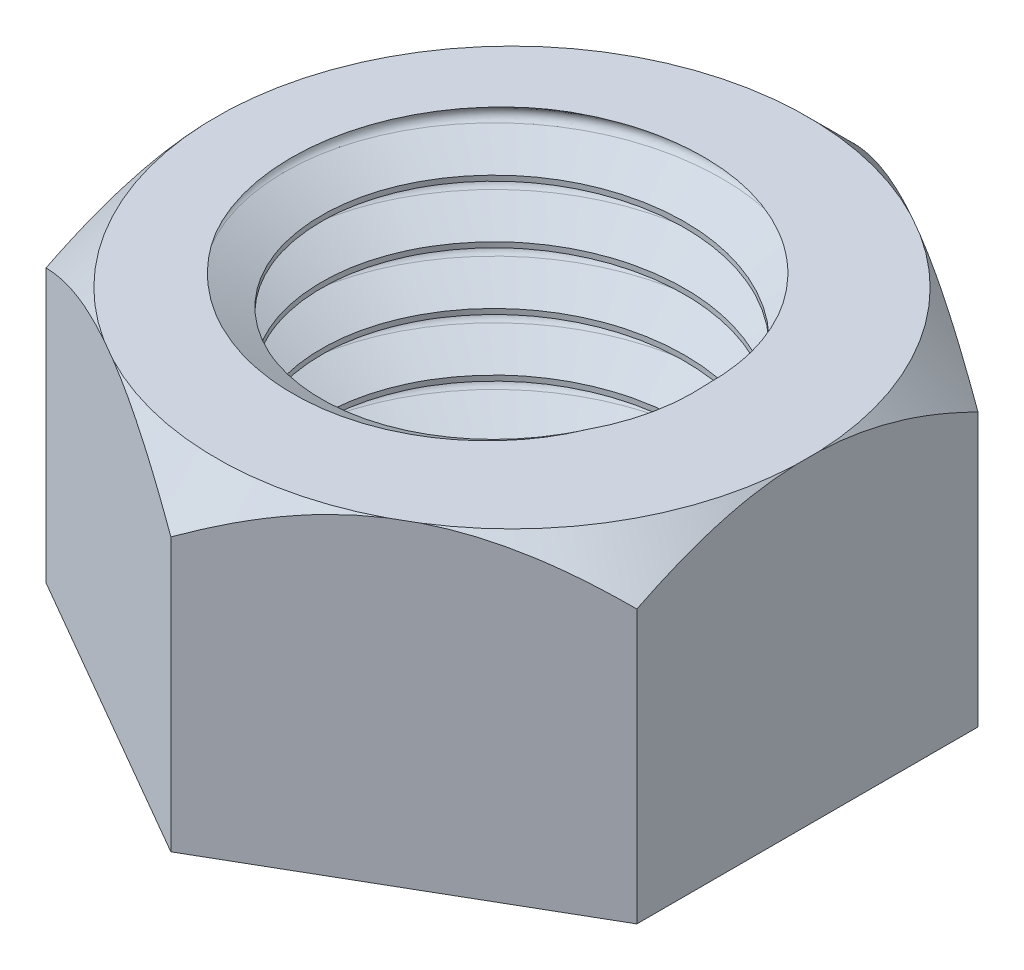
SolidWorks part; units mm, degrees
ref_plane "Alzado" through (0, 0, 0) normal (0, 0, 1) x (1, 0, 0)
ref_plane "Planta" through (0, 0, 0) normal (0, 1, 0) x (1, 0, 0)
ref_plane "Vista lateral" through (0, 0, 0) normal (1, 0, 0) x (0, 0, -1)
sketch "Sketch1" plane through (0, 0, 0) normal (0, 1, 0) x (1, 0, 0)
  line L1 (6.5, -3.7528) -> (6.5, 3.7528)
  line L2 (6.5, 3.7528) -> (0, 7.5056)
  line L3 (0, 7.5056) -> (-6.5, 3.7528)
  line L4 (-6.5, 3.7528) -> (-6.5, -3.7528)
  line L5 (-6.5, -3.7528) -> (0, -7.5056)
  line L6 (0, -7.5056) -> (6.5, -3.7528)
  circle A0 centre (0, 0) radius 6.5 construction
  circle A1 centre (0, 0) radius 4
  dimension "D2" = 8
  dimension "D1" = 13
extrude "Boss-Extrude1" add sketch "Sketch1" along normal blind 7
sketch "Sketch2" plane through (0, 7, 0) normal (0, 1, 0) x (1, 0, 0)
  circle A0 centre (0, 0) radius 4 construction
  circle A1 centre (0, 0) radius 4
curve "Helix/Spiral1" pitch 1.27 height 7.62 turns 6
sketch "Sketch3" plane through (0, 0, 0) normal (0, 0, 1) x (1, 0, 0)
  line L0 (-3.9127, 0.0452) -> (-4.813, -0.4235)
  line L1 (-4.813, -0.7322) -> (-3.9127, -1.2009)
  line L2 (-3.9127, -1.2009) -> (-3.9127, 0.0452)
  line L3 (-4.7327, -0.5778) -> (-3.9127, -0.5778) construction
  arc A0 (-4.813, -0.4235) -> (-4.813, -0.7322) centre (-4.7327, -0.5778) ccw
  spline S0 degree 3 poles (-4, 7) (-4, 6.9737) (-3.7917, 6.9205) (-2.9021, 6.8413) (-1.5706, 6.7619) (0, 6.6825) (1.5706, 6.6031) (2.9021, 6.5238) (3.7917, 6.4444) (4.1041, 6.365) (3.7917, 6.2856) (2.9021, 6.2063) (1.1268, 6.1004) (-1.1268, 5.9946) (-2.9021, 5.8888) (-3.7917, 5.8094) (-4.1041, 5.73) (-3.7917, 5.6506) (-2.9021, 5.5713) (-1.1268, 5.4654) (1.1268, 5.3596) (2.9021, 5.2537) (3.7917, 5.1744) (4.1041, 5.095) (3.7917, 5.0156) (2.9021, 4.9362) (1.1268, 4.8304) (-1.1268, 4.7246) (-2.9021, 4.6187) (-3.7917, 4.5394) (-4.1041, 4.46) (-3.7917, 4.3806) (-2.9021, 4.3012) (-1.1268, 4.1954) (1.1268, 4.0896) (2.9021, 3.9837) (3.7917, 3.9044) (4.1041, 3.825) (3.7917, 3.7456) (2.9021, 3.6662) (1.1268, 3.5604) (-1.1268, 3.4546) (-2.9021, 3.3487) (-3.7917, 3.2694) (-4.1041, 3.19) (-3.7917, 3.1106) (-2.9021, 3.0313) (-1.1268, 2.9254) (1.1268, 2.8196) (2.9021, 2.7138) (3.7917, 2.6344) (4.1041, 2.555) (3.7917, 2.4756) (2.9021, 2.3963) (1.1268, 2.2904) (-1.1268, 2.1846) (-2.9021, 2.0788) (-3.7917, 1.9994) (-4.1041, 1.92) (-3.7917, 1.8406) (-2.9021, 1.7613) (-1.1268, 1.6554) (1.1268, 1.5496) (2.9021, 1.4438) (3.7917, 1.3644) (4.1041, 1.285) (3.7917, 1.2056) (2.9021, 1.1263) (1.1268, 1.0204) (-1.1268, 0.9146) (-2.9021, 0.8087) (-3.7917, 0.7294) (-4.1041, 0.65) (-3.7917, 0.5706) (-2.9021, 0.4912) (-1.1268, 0.3854) (1.1268, 0.2796) (2.9021, 0.1737) (3.7917, 0.0944) (4.1041, 0.015) (3.7917, -0.0644) (2.9021, -0.1438) (1.5706, -0.2231) (0, -0.3025) (-1.5706, -0.3819) (-2.9021, -0.4613) (-3.7917, -0.5405) (-4, -0.5937) (-4, -0.62) knots 0 0 0 0 0.010417 0.020833 0.03125 0.041667 0.052083 0.0625 0.072917 0.083333 0.09375 0.104167 0.114583 0.135417 0.145833 0.15625 0.166667 0.177083 0.1875 0.197917 0.21875 0.229167 0.239583 0.25 0.260417 0.270833 0.28125 0.302083 0.3125 0.322917 0.333333 0.34375 0.354167 0.364583 0.385417 0.395833 0.40625 0.416667 0.427083 0.4375 0.447917 0.46875 0.479167 0.489583 0.5 0.510417 0.520833 0.53125 0.552083 0.5625 0.572917 0.583333 0.59375 0.604167 0.614583 0.635417 0.645833 0.65625 0.666667 0.677083 0.6875 0.697917 0.71875 0.729167 0.739583 0.75 0.760417 0.770833 0.78125 0.802083 0.8125 0.822917 0.833333 0.84375 0.854167 0.864583 0.885417 0.895833 0.90625 0.916667 0.927083 0.9375 0.947917 0.958333 0.96875 0.979167 0.989583 1 1 1 1 construction
  dimension "D1" = 0.174
  dimension "D2" = 55
  dimension "D3" = 0.82
sweep "Cut-Sweep1" cut profiles "Sketch3" path "Helix/Spiral1" align with end faces yes
sketch "Sketch4" plane through (0, 0, 0) normal (0, -1, 0) x (-1, 0, 0)
  circle A0 centre (0, 0) radius 6.35
ref_plane "Plane1" through (0, 0, 0) normal (-0.5, 0, 0.866) x (0.866, 0, 0.5)
sketch "Sketch5" plane through (0, 0, 0) normal (-0.5, 0, 0.866) x (0.866, 0, 0.5)
  line L0 (6.5056, 7) -> (7.5056, 6)
  line L1 (3.7528, 7) -> (7.5056, 7) construction
  line L2 (7.5056, 7) -> (7.5056, 0) construction
  line L3 (7.5056, 6) -> (7.5056, 7)
  line L4 (7.5056, 7) -> (6.5056, 7)
  line L5 (0, 0) -> (0, 4.094) construction
  dimension "D1" = 1
  dimension "D2" = 1
revolve "Cut-Revolve1" cut sketch "Sketch5" angle 360 about L5
